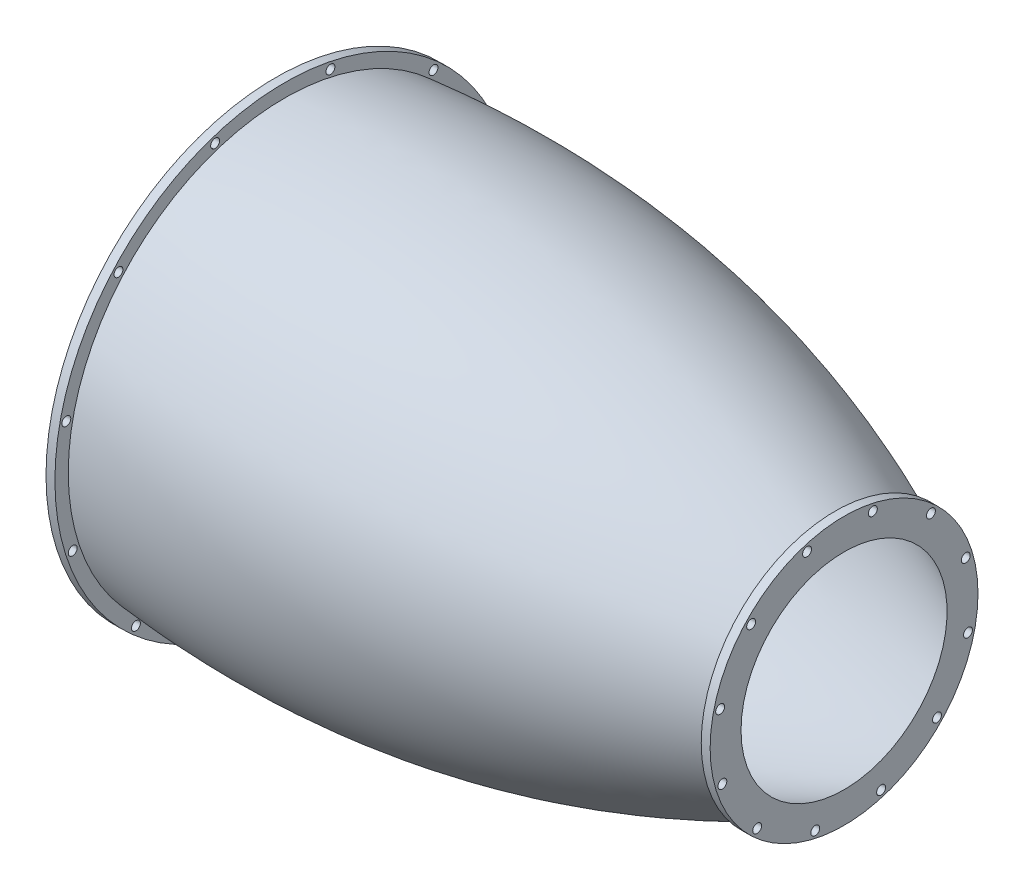
SolidWorks part; units mm, degrees
material "Copper"
ref_plane "Front Plane" through (0, 0, 0) normal (0, 0, 1) x (1, 0, 0)
ref_plane "Top Plane" through (0, 0, 0) normal (0, 1, 0) x (1, 0, 0)
ref_plane "Right Plane" through (0, 0, 0) normal (1, 0, 0) x (0, 0, -1)
sketch "Sketch1" plane through (0, 0, 0) normal (0, 0, 1) x (1, 0, 0)
  line L0 (-1229.8282, 0) -> (1426.3964, 0) construction
  line L1 (0, -70.104) -> (0, 70.104) construction
  line L2 (0, 0) -> (500, 0) construction
  line L3 (500, -330.2) -> (500, 330.2) construction
  line L5 (500, 339.09) -> (500, 330.2)
  line L6 (0, -78.994) -> (0, -70.104)
  line L7 (500, -339.09) -> (500, -330.2)
  line L8 (-412.8242, -144.8099) -> (-412.8242, 144.8099) construction
  line L9 (-412.8242, 144.8099) -> (-412.8242, 153.6999)
  line L10 (-412.8242, -144.8099) -> (-412.8242, -153.6999)
  spline S0 degree 2 poles (0, 70.104) (170.2621, 318.867) (500, 330.2) knots 0 0 0 1 1 1
  spline S1 degree 2 poles (0, -70.104) (170.2621, -318.867) (500, -330.2) knots 0 0 0 1 1 1
  spline S2 degree 2 poles (0, -78.994) (170.2621, -327.757) (500, -339.09) knots 0 0 0 1 1 1
  spline S3 degree 2 poles (0, -70.104) (170.2621, -318.867) (500, -330.2) knots 0 0 0 1 1 1
  spline S4 degree 2 poles (0, 78.994) (170.2621, 327.757) (500, 339.09) knots 0 0 0 1 1 1
  spline S5 degree 2 poles (0, 70.104) (-195.4497, 157.4108) (-412.8242, 144.8099) knots 0 0 0 1 1 1
  spline S6 degree 2 poles (0, -70.104) (-195.4497, -157.4108) (-412.8242, -144.8099) knots 0 0 0 1 1 1
  spline S7 degree 2 poles (0, -78.994) (-192.7304, -176.7061) (-412.8242, -153.6999) knots 0 0 0 1 1 1
  spline S9 degree 2 poles (0, 78.994) (-192.7304, 176.7061) (-412.8242, 153.6999) knots 0 0 0 1 1 1
  point P8 (0, 0)
  point P14 (500, 0)
  point P22 (-412.8242, 0)
  dimension "D4" = 8.89
  dimension "D1" = 140.208
  dimension "D2" = 500
  dimension "D3" = 660.4
  dimension "D5" = 8.89
  dimension "D6" = 8.89
  dimension "D7" = 289.6197
revolve "Revolve3" add sketch "Sketch1" angle 360 about L0 region at (490.4837, 334.645, 0)
ref_plane "Plane1" through (0, 0, 0) normal (1, 0, 0) x (0, 0, -1)
ref_plane "Plane2" through (-7.62, 0, 0) normal (-1, 0, 0) x (0, 0, 1)
sketch "Sketch4" plane through (-7.62, 0, 0) normal (-1, 0, 0) x (0, 0, 1)
  line L1 (-1213.2286, 638.9142) -> (1085.9115, 638.9142)
  line L2 (-1213.2286, 638.9142) -> (-1213.2286, -445.9528)
  line L3 (-1213.2286, -445.9528) -> (1085.9115, -445.9528)
  line L4 (1085.9115, 638.9142) -> (1085.9115, -445.9528)
extrude "Cut-Extrude1" cut sketch "Sketch4" against normal blind 782.066
ref_plane "Plane3" through (-7.62, 0, 0) normal (1, 0, 0) x (0, 0, -1)
sketch "Sketch5" plane through (-7.62, 0, 0) normal (1, 0, 0) x (0, 0, -1)
  circle A0 centre (0, 0) radius 82.8048 construction
  circle A1 centre (0, 0) radius 82.8048
  circle A2 centre (0, 0) radius 95.5048
  dimension "D1" = 12.7
extrude "Boss-Extrude1" add sketch "Sketch5" against normal blind 6.35
ref_plane "Plane4" through (-412.8242, 0, 0) normal (-1, 0, 0) x (0, 0, 1)
sketch "Sketch6" plane through (-412.8242, 0, 0) normal (-1, 0, 0) x (0, 0, 1)
  circle A0 centre (0, 0) radius 153.6999 construction
  circle A1 centre (0, 0) radius 153.6999
  circle A2 centre (0, 0) radius 163.8599
  dimension "D1" = 10.16
extrude "Boss-Extrude2" add sketch "Sketch6" against normal blind 6.35 contours A2 | A1
ref_plane "Plane5" through (-13.97, 0, 0) normal (-1, 0, 0) x (0, 0, 1)
sketch "Sketch7" plane through (-13.97, 0, 0) normal (-1, 0, 0) x (0, 0, 1)
  line L0 (0, 0) -> (21.6047, -93.0291) construction
  line L1 (21.6047, -93.0291) -> (19.4321, -83.674) construction
  circle A1 centre (0, 0) radius 95.5048
  circle A2 centre (0, 0) radius 95.5048
  circle A3 centre (0, 0) radius 85.9007 construction
  circle A4 centre (0, 0) radius 85.9007
  point P7 (20.5184, -88.3515)
  dimension "D1" = 0
hole_wizard "1/4 (0.25) Diameter Hole1" positions "3DSketch1" profile "Sketch8" hole size "1/4" standard "ANSI Inch"
sketch3d "3DSketch1"
  point P0 (-13.97, -88.3515, 20.5184)
sketch "Sketch8" plane through (-13.97, -88.3515, 20.5184) normal (0, 1, 0) x (0, 0, 1)
  line L0 (0, 0) -> (0, 8.2577)
  line L1 (0, 8.2577) -> (3.175, 6.35)
  line L2 (3.175, 6.35) -> (3.175, 0)
  line L5 (3.175, 0) -> (0, 0)
  line L10 (0, 8.2577) -> (-3.175, 6.35) construction
  line L11 (0, -6.35) -> (0, 107.95) construction
  dimension "Hole Dia." = 6.35
  dimension "Hole Depth" = 6.35
  dimension "Drill Angle" = 118
pattern_circular "CirPattern1" count 12 over 360 about axis through (-13.97, 0, 0) along (1, 0, 0) of "1/4 (0.25) Diameter Hole1" reverse direction yes
ref_plane "Plane6" through (-406.4742, 0, 0) normal (1, 0, 0) x (0, 0, -1)
sketch "Sketch9" plane through (-406.4742, 0, 0) normal (1, 0, 0) x (0, 0, -1)
  line L0 (0, 0) -> (-33.5856, -160.381) construction
  line L1 (-33.5856, -160.381) -> (-31.6341, -151.0623) construction
  circle A0 centre (0, 0) radius 163.8599 construction
  circle A1 centre (0, 0) radius 163.8599
  circle A2 centre (0, 0) radius 154.3391 construction
  circle A3 centre (0, 0) radius 154.3391
  point P6 (-32.6098, -155.7217)
hole_wizard "1/4 (0.25) Diameter Hole2" positions "3DSketch2" profile "Sketch10" hole size "1/4" standard "ANSI Inch"
sketch3d "3DSketch2"
  point P0 (-406.4742, -155.7217, 32.6098)
sketch "Sketch10" plane through (-406.4742, -155.7217, 32.6098) normal (0, 1, 0) x (0, 0, -1)
  line L0 (0, 0) -> (0, 8.2577)
  line L1 (0, 8.2577) -> (3.175, 6.35)
  line L2 (3.175, 6.35) -> (3.175, 0)
  line L5 (3.175, 0) -> (0, 0)
  line L10 (0, 8.2577) -> (-3.175, 6.35) construction
  line L11 (0, -6.35) -> (0, 107.95) construction
  dimension "Hole Dia." = 6.35
  dimension "Hole Depth" = 6.35
  dimension "Drill Angle" = 118
pattern_circular "CirPattern2" count 12 over 360 about axis through (-406.4742, 0, 0) along (-1, 0, 0) of "1/4 (0.25) Diameter Hole2" reverse direction yes
